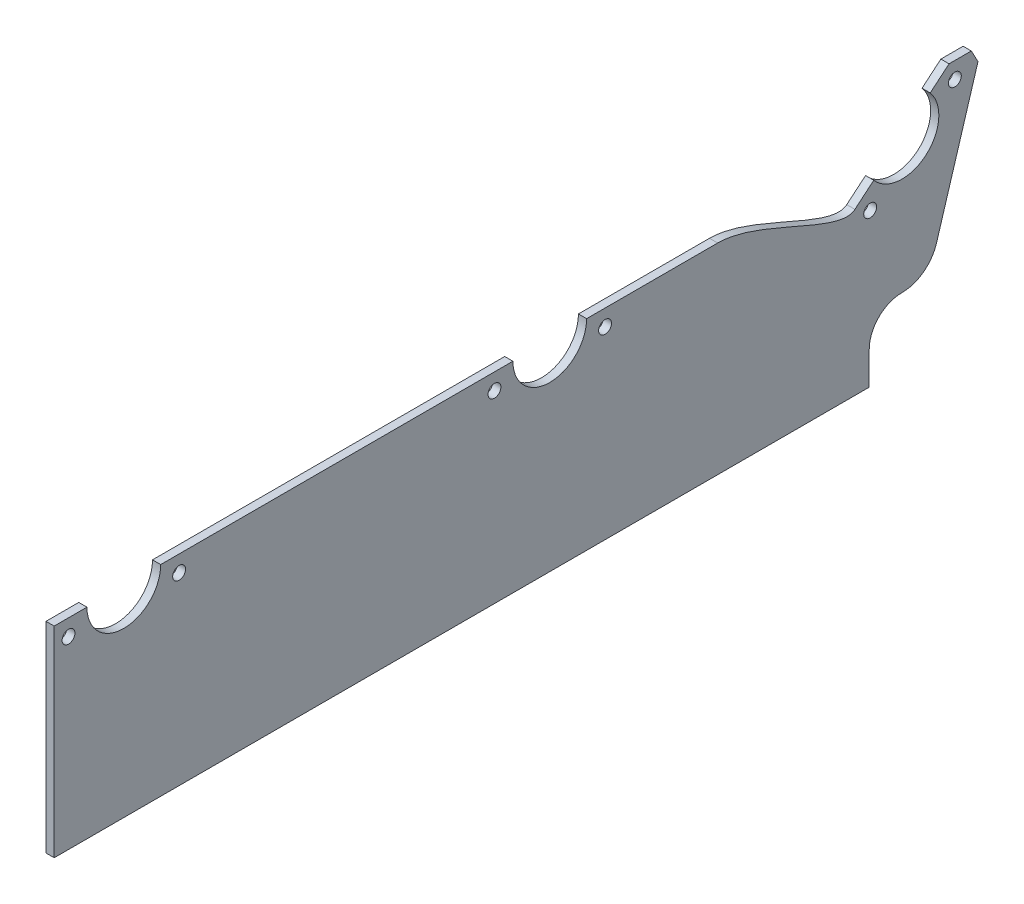
SolidWorks part; units mm, degrees
material "6061 Alloy"
ref_plane "Front Plane" through (0, 0, 0) normal (0, 0, 1) x (1, 0, 0)
ref_plane "Top Plane" through (0, 0, 0) normal (0, 1, 0) x (1, 0, 0)
ref_plane "Right Plane" through (0, 0, 0) normal (1, 0, 0) x (0, 0, -1)
sketch "Sketch1" plane through (0, 0, 0) normal (1, 0, 0) x (0, 0, -1)
  line L0 (-12.7, -12.7) -> (-328.6125, -12.7)
  line L1 (-328.6125, -12.7) -> (-328.6125, 65.0875)
  line L2 (-328.6125, 65.0875) -> (-315.9125, 65.0875)
  line L3 (-287.3375, 65.0875) -> (-150.8125, 65.0875)
  line L5 (10.9449, 74.2713) -> (18.2432, 80.3953)
  line L7 (-328.6125, 12.7) -> (13.3654, 12.7) construction
  line L8 (-12.7, -12.7) -> (-12.7, 0)
  line L9 (0, 12.4079) -> (0, 12.7) construction
  line L10 (13.3654, 22.6047) -> (30.9432, 80.3953)
  line L12 (-10.9449, 55.9037) -> (10.9449, 74.2713) construction
  line L13 (18.2432, 80.3953) -> (30.9432, 80.3953)
  line L14 (-122.2375, 65.0875) -> (-71.4375, 65.0875)
  line L15 (-10.9449, 55.9037) -> (-18.2432, 49.7797)
  line L18 (0, 65.0875) -> (-136.525, 65.0875) construction
  arc A3 (0, 12.7) -> (13.3654, 22.6047) centre (0, 26.67) ccw
  arc A4 (0, 12.7) -> (-12.7, 0) centre (0, 0) ccw
  circle A5 centre (0, 0) radius 12.4079 construction
  arc A6 (-315.9125, 65.0875) -> (-287.3375, 65.0875) centre (-301.625, 65.0875) ccw
  arc A7 (-150.8125, 65.0875) -> (-122.2375, 65.0875) centre (-136.525, 65.0875) ccw
  arc A8 (-10.9449, 55.9037) -> (10.9449, 74.2713) centre (0, 65.0875) ccw
  spline S0 degree 3 poles (-18.2432, 49.7797) (-24.729, 44.3374) (-54.5042, 65.0875) (-71.4375, 65.0875) knots 0 0 0 0 1 1 1 1
  point P4 (-170.6562, -12.7)
  point P21 (-55.0714, 65.0875)
  dimension "D1" = 25.4
  dimension "D3" = 12.7
  dimension "D5" = 28.575
  dimension "D6" = 38.1
  dimension "D7" = 13.97
  dimension "D8" = 12.7
  dimension "D10" = 24.8158
  dimension "D13" = 9.5273
  dimension "D14" = 140
  dimension "D15" = 50.8
  dimension "D16" = 50.8
  dimension "D17" = 25.4
  dimension "D2" = 0
  dimension "D4" = 12.7
  dimension "D9" = 12.7
  dimension "D11" = 301.625
  dimension "D12" = 301.625
extrude "Boss-Extrude1" add sketch "Sketch1" along normal blind 3.175
hole_wizard "#10 Clearance Hole1" positions "Sketch2" profile "Sketch3" hole size "#10" standard "ANSI Inch" end condition through all
sketch "Sketch2" plane through (3.175, 0, 0) normal (1, 0, 0) x (0, 0, -1)
  line L0 (-323.0562, 58.7375) -> (-280.1937, 58.7375) construction
  line L2 (-157.9562, 58.7375) -> (-115.0937, 58.7375) construction
  line L4 (-12.3356, 46.4474) -> (20.499, 73.9989) construction
  line L6 (-315.9125, 65.0875) -> (-328.6125, 65.0875) construction
  line L7 (-301.625, 58.7375) -> (-301.625, 65.0875) construction
  line L9 (-136.525, 65.0875) -> (-136.525, 58.7375) construction
  line L11 (0, 65.0875) -> (4.0817, 60.2231) construction
  line L14 (18.2432, 80.3953) -> (10.9449, 74.2713) construction
  line L15 (18.2432, 80.3953) -> (10.9449, 74.2713) construction
  point P0 (-323.0562, 58.7375)
  point P2 (-280.1938, 58.7375)
  point P4 (-157.9562, 58.7375)
  point P6 (-115.0937, 58.7375)
  point P8 (-12.3356, 46.4474)
  point P10 (20.499, 73.9989)
  dimension "D1" = 42.8625
  dimension "D2" = 6.35
  dimension "D3" = 6.35
sketch "Sketch3" plane through (3.175, 58.7375, 323.0562) normal (0, 1, 0) x (0, 0, -1)
  line L0 (0, 0) -> (0, 3.175)
  line L1 (0, 3.175) -> (2.4892, 3.175)
  line L2 (2.4892, 3.175) -> (2.4892, 0)
  line L5 (2.4892, 0) -> (0, 0)
  line L11 (0, -6.35) -> (0, 107.95) construction
  dimension "Thru Hole Dia." = 4.9784
  dimension "Thru Hole Depth" = 3.175
chamfer "Chamfer1" distance 5.08 angle 45 1 edges at (1.5875, 80.3953, -30.9432) first distance on face at (1.5875, 51.5, -22.1543)
